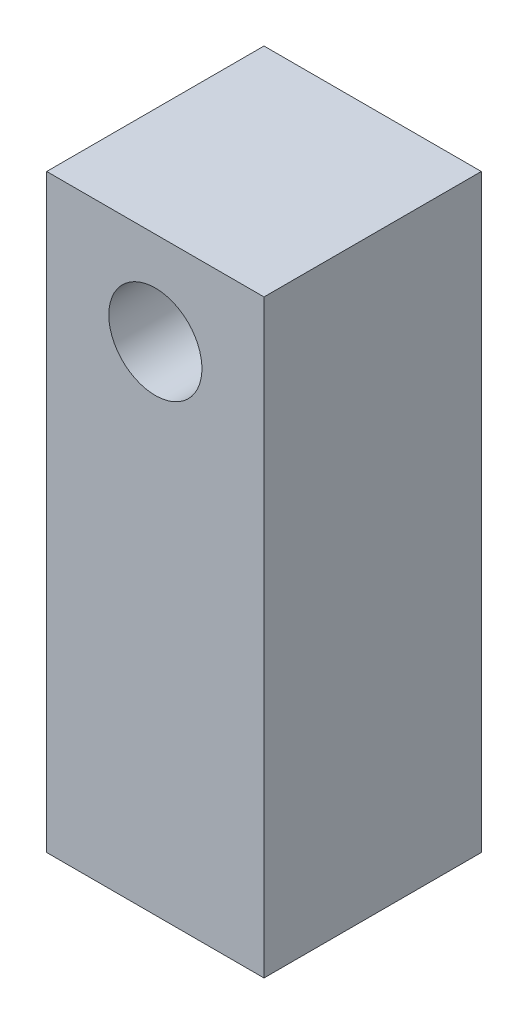
SolidWorks part; units mm, degrees
material "PLA"
ref_plane "Front Plane" through (0, 0, 0) normal (0, 0, 1) x (1, 0, 0)
ref_plane "Top Plane" through (0, 0, 0) normal (0, 1, 0) x (1, 0, 0)
ref_plane "Right Plane" through (0, 0, 0) normal (1, 0, 0) x (0, 0, -1)
sketch "Sketch1" plane through (0, 0, 0) normal (0, 1, 0) x (1, 0, 0)
  line L1 (-3.5, -3.5) -> (3.5, -3.5)
  line L2 (-3.5, -3.5) -> (-3.5, 3.5)
  line L3 (-3.5, 3.5) -> (3.5, 3.5)
  line L4 (3.5, -3.5) -> (3.5, 3.5)
  line L5 (-3.5, -3.5) -> (3.5, 3.5) construction
  line L6 (-3.5, 3.5) -> (3.5, -3.5) construction
  circle A1 centre (0, 0) radius 2
  dimension "D1" = 7
  dimension "D2" = 4
extrude "Boss-Extrude1" add sketch "Sketch1" along normal blind 13
sketch "Sketch2" plane through (0, 0, 0) normal (0, 0, 1) x (1, 0, 0)
  line L2 (-3.5, 19) -> (3.5, 19)
  line L3 (-3.5, 19) -> (-3.5, 13)
  line L4 (-3.5, 13) -> (3.5, 13)
  line L5 (3.5, 19) -> (3.5, 13)
  line L6 (-3.5, 19) -> (3.5, 13) construction
  line L7 (-3.5, 13) -> (3.5, 19) construction
  circle A1 centre (0, 16) radius 1.5
  dimension "D1" = 6
  dimension "D2" = 3
extrude "Boss-Extrude2" add sketch "Sketch2" along normal up to surface and the other way up to surface up to face at (0, 6.5, 3.5) other way up to face at (0, 6.5, -3.5)
